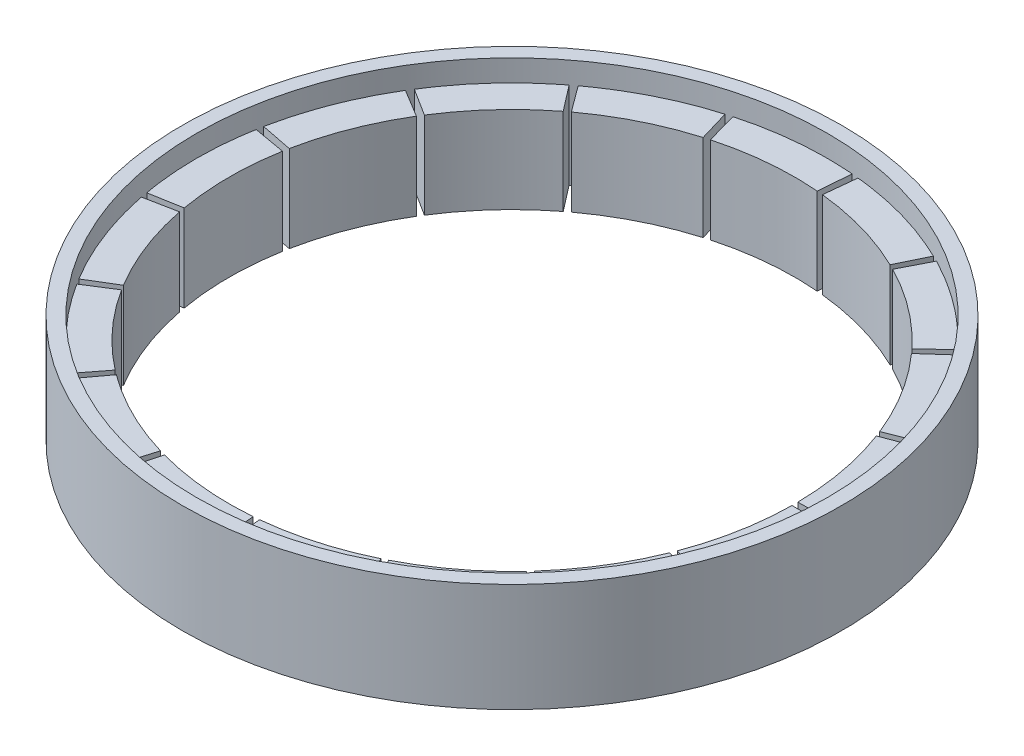
SolidWorks part; units mm, degrees
ref_plane "Front Plane" through (0, 0, 0) normal (0, 0, 1) x (1, 0, 0)
ref_plane "Top Plane" through (0, 0, 0) normal (0, 1, 0) x (1, 0, 0)
ref_plane "Right Plane" through (0, 0, 0) normal (1, 0, 0) x (0, 0, -1)
ref_axis "Axis1" through (0, 0, 0) along (0, 1, 0)
sketch "Sketch1" plane through (0, 0, 0) normal (0, 0, 1) x (1, 0, 0)
  line L0 (0, 0) -> (0, -67318.1224) construction
  line L1 (-25.9, 14.75) -> (-25.9, 6.75) construction
  line L2 (-30.4, 16.75) -> (-29.1, 16.75)
  line L3 (-30.4, 16.75) -> (-30.4, 6.75)
  line L4 (-30.4, 6.75) -> (-29.1, 6.75)
  line L5 (-29.1, 16.75) -> (-29.1, 6.75)
  dimension "D1" = 10
  dimension "D2" = 1.3
  dimension "D3" = 3.2
revolve "Revolve1" add sketch "Sketch1" angle 360 about L0
sketch "Sketch2" plane through (0, 0, 0) normal (0, 0, 1) x (1, 0, 0)
  line L0 (29.1, 16.75) -> (-29.1, 16.75) construction
  line L1 (-29.1, 6.75) -> (-26.1, 6.75)
  line L2 (-29.1, 6.75) -> (-29.1, 14.75)
  line L3 (-29.1, 14.75) -> (-26.1, 14.75)
  line L4 (-26.1, 6.75) -> (-26.1, 14.75)
  line L5 (-30.4, 16.75) -> (-30.4, 6.75) construction
  dimension "D1" = 2
  dimension "D2" = 4.3
revolve "Revolve2" add sketch "Sketch2" angle 20 mid plane about axis through (0, 0, 0) along (0, 1, 0)
pattern_circular "CirPattern2" count 17 over 360 about axis through (0, 0, 0) along (0, 1, 0) of bodies 102
